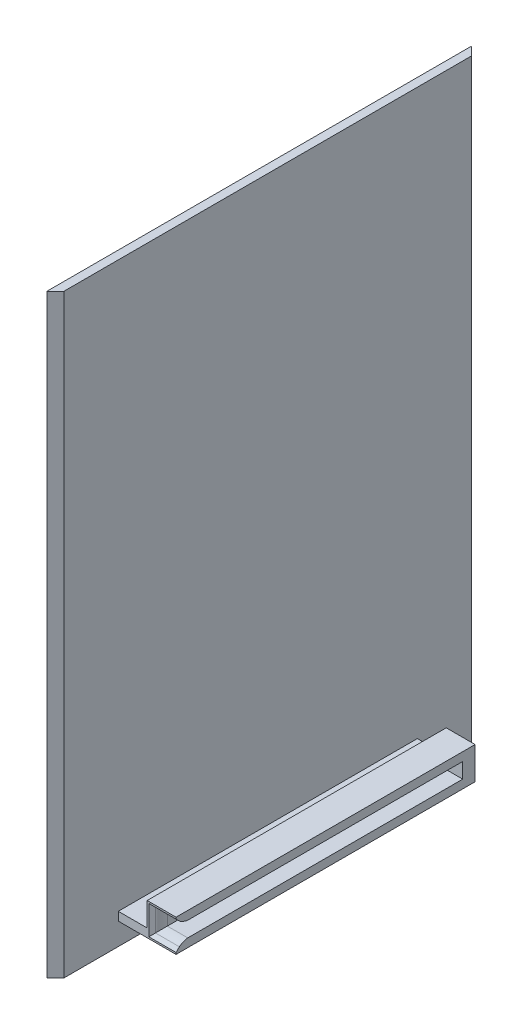
SolidWorks part; units mm, degrees
material "ABS"
ref_plane "Alzado" through (0, 0, 0) normal (0, 0, 1) x (1, 0, 0)
ref_plane "Planta" through (0, 0, 0) normal (0, 1, 0) x (1, 0, 0)
ref_plane "Vista lateral" through (0, 0, 0) normal (1, 0, 0) x (0, 0, -1)
sketch "Croquis1" plane through (0, 0, 0) normal (0, 1, 0) x (1, 0, 0)
  line L0 (0, 0) -> (0, 250)
  line L1 (0, 250) -> (-5, 250)
  line L2 (-5, 250) -> (-5, 0)
  line L3 (-5, 0) -> (0, 0)
  dimension "D1" = 250
  dimension "D2" = 250
  dimension "D3" = 5
extrude "Saliente-Extruir1" add sketch "Croquis1" along normal blind 350
sketch "Croquis2" plane through (0, 350, 0) normal (0, 1, 0) x (1, 0, 0)
  line L0 (0, 250) -> (0, 245)
  line L1 (0, 0) -> (0, 250) construction
  line L2 (0, 245) -> (-5, 250)
  line L3 (-5, 250) -> (0, 250)
  line L4 (-5, 0) -> (0, 5)
  line L5 (0, 5) -> (0, 0)
  line L6 (0, 0) -> (-5, 0)
  dimension "D1" = 5
  dimension "D2" = 5
extrude "Cortar-Extruir1" cut sketch "Croquis2" against normal up to next
sketch "Croquis4" plane through (0, 0, 0) normal (1, 0, 0) x (0, 0, -1)
  line L1 (37, 13) -> (213, 13)
  line L2 (37, 13) -> (37, 18)
  line L3 (37, 18) -> (213, 18)
  line L4 (213, 13) -> (213, 18)
  line L5 (245, 0) -> (245, 350) construction
  line L6 (5, 0) -> (5, 350) construction
  line L7 (5, 0) -> (245, 0) construction
  dimension "D1" = 5
  dimension "D2" = 18
  dimension "D3" = 32
  dimension "D4" = 32
extrude "Saliente-Extruir2" add sketch "Croquis4" along normal blind 34
sketch "Croquis5" plane through (0, 18, 0) normal (0, 1, 0) x (1, 0, 0)
  line L0 (34, 213) -> (0, 213) construction
  line L1 (17, 213) -> (22, 213)
  line L2 (17, 213) -> (17, 37)
  line L3 (17, 37) -> (22, 37)
  line L4 (22, 213) -> (22, 37)
  line L5 (34, 37) -> (0, 37) construction
  dimension "D1" = 12
  dimension "D2" = 5
extrude "Saliente-Extruir3" add sketch "Croquis5" along normal blind 9
sketch "Croquis6" plane through (0, 27, 0) normal (0, 1, 0) x (1, 0, 0)
  line L1 (17, 213) -> (34, 213)
  line L2 (17, 213) -> (17, 37)
  line L3 (17, 37) -> (34, 37)
  line L4 (34, 213) -> (34, 37)
extrude "Saliente-Extruir4" add sketch "Croquis6" along normal blind 5
chamfer "Chaflán1" distance 4 3 edges at (28, 18, -37) (22, 22.5, -37) (28, 27, -37)
fillet "Redondeo1" radius 7 3 edges at (28, 18, -41) (22, 22.5, -41) (28, 27, -41) conic rho 0.3
sketch "Croquis7" plane through (0, 18, 0) normal (0, 1, 0) x (1, 0, 0)
  line L1 (34, 213) -> (19.4177, 213)
  line L2 (34, 213) -> (34, 205.7)
  line L3 (34, 205.7) -> (19.4177, 205.7)
  line L4 (19.4177, 213) -> (19.4177, 205.7)
  dimension "D1" = 7.3
extrude "Saliente-Extruir5" add sketch "Croquis7" along normal blind 10
